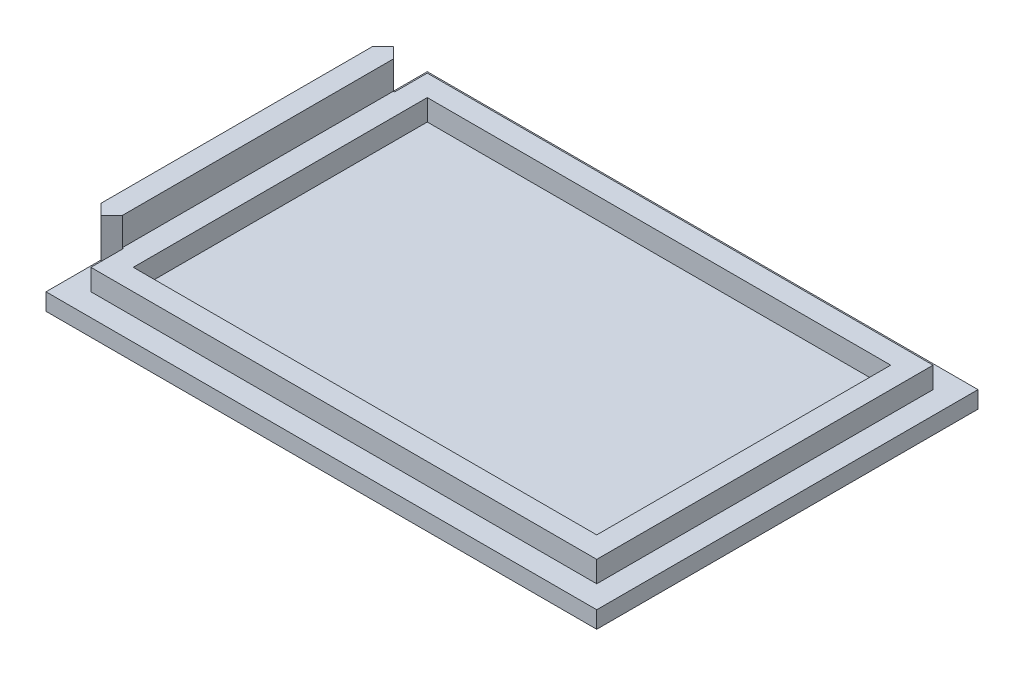
SolidWorks part; units mm, degrees
ref_plane "前视基准面" through (0, 0, 0) normal (0, 0, 1) x (1, 0, 0)
ref_plane "上视基准面" through (0, 0, 0) normal (0, 1, 0) x (1, 0, 0)
ref_plane "右视基准面" through (0, 0, 0) normal (1, 0, 0) x (0, 0, -1)
sketch "草图1" plane through (0, 0, 0) normal (0, 1, 0) x (1, 0, 0)
  line L1 (-32.5, 22.5) -> (32.5, 22.5)
  line L2 (-32.5, 22.5) -> (-32.5, -22.5)
  line L3 (-32.5, -22.5) -> (32.5, -22.5)
  line L4 (32.5, 22.5) -> (32.5, -22.5)
  line L5 (-32.5, 22.5) -> (32.5, -22.5) construction
  line L6 (-32.5, -22.5) -> (32.5, 22.5) construction
  point P0 (0, 0)
  dimension "D1" = 65
  dimension "D2" = 45
extrude "凸台-拉伸1" add sketch "草图1" along normal blind 2
sketch "草图2" plane through (0, 2, 0) normal (0, 1, 0) x (1, 0, 0)
  line L1 (-29.85, -19.85) -> (29.85, -19.85)
  line L2 (-29.85, -19.85) -> (-29.85, 19.85)
  line L3 (-29.85, 19.85) -> (29.85, 19.85)
  line L4 (29.85, -19.85) -> (29.85, 19.85)
  line L5 (-29.85, -19.85) -> (29.85, 19.85) construction
  line L6 (-29.85, 19.85) -> (29.85, -19.85) construction
  point P0 (0, 0)
  dimension "D1" = 39.7
  dimension "D2" = 59.7
extrude "凸台-拉伸2" add sketch "草图2" along normal blind 2.5
sketch "草图3" plane through (0, 2, 0) normal (0, 1, 0) x (1, 0, 0)
  line L0 (0, 0) -> (-42.5396, 0) construction
  line L1 (-32.5, 22.5) -> (-32.5, -22.5) construction
  line L2 (-30, -16) -> (-29.85, -16)
  line L3 (-32.5, -16) -> (-32.5, 16)
  line L4 (-30, 16) -> (-29.85, 16)
  line L5 (-29.85, -16) -> (-29.85, 16)
  line L6 (-29.85, 19.85) -> (-29.85, -19.85) construction
  line L7 (-32.5, 16) -> (-31.25, 17.25)
  line L8 (-31.25, 17.25) -> (-30, 16)
  line L9 (-32.5, -16) -> (-31.25, -17.25)
  line L10 (-31.25, -17.25) -> (-30, -16)
  dimension "D1" = 32
  dimension "D2" = 16
  dimension "D3" = 2.5
  dimension "D4" = 2.5
extrude "凸台-拉伸3" add sketch "草图3" along normal blind 5.8
sketch "草图4" plane through (0, 7.8, 0) normal (0, 1, 0) x (1, 0, 0)
  line L1 (-29.85, 16) -> (-30, 16)
  line L2 (-29.85, 16) -> (-29.85, -16)
  line L3 (-29.85, -16) -> (-30, -16)
  line L4 (-30, 16) -> (-30, -16)
extrude "切除-拉伸1" cut sketch "草图4" against normal up to surface (3.3 mm away) up to face at (-9.95, 4.5, 0)
sketch "草图5" plane through (0, 4.5, 0) normal (0, 1, 0) x (1, 0, 0)
  line L0 (29.85, 19.85) -> (-29.85, 19.85) construction
  line L1 (-27.35, -17.35) -> (27.35, -17.35)
  line L2 (-27.35, -17.35) -> (-27.35, 17.35)
  line L3 (-27.35, 17.35) -> (27.35, 17.35)
  line L4 (27.35, -17.35) -> (27.35, 17.35)
  line L5 (-27.35, -17.35) -> (27.35, 17.35) construction
  line L6 (-27.35, 17.35) -> (27.35, -17.35) construction
  line L7 (29.85, -19.85) -> (29.85, 19.85) construction
  point P0 (0, 0)
  dimension "D1" = 2.5
  dimension "D2" = 2.5
extrude "切除-拉伸2" cut sketch "草图5" against normal up to surface (2.5 mm away) up to face at (-15.45, 2, 0)
